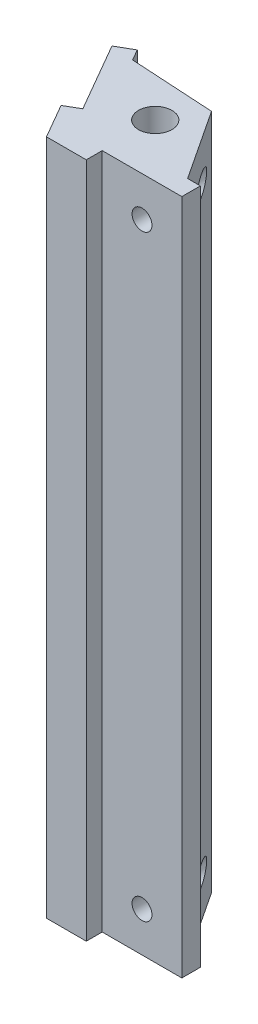
SolidWorks part; units mm, degrees
material "6061-T6 (SS)"
ref_plane "Front Plane" through (0, 0, 0) normal (0, 0, 1) x (1, 0, 0)
ref_plane "Top Plane" through (0, 0, 0) normal (0, 1, 0) x (1, 0, 0)
ref_plane "Right Plane" through (0, 0, 0) normal (1, 0, 0) x (0, 0, -1)
sketch "Sketch1" plane through (0, 0, 0) normal (0, 1, 0) x (1, 0, 0)
  line L0 (0, 0) -> (15, 0)
  line L1 (0, 0) -> (-7.5, 12.9904)
  line L2 (15, 0) -> (15, 4.3301)
  line L3 (0, 0) -> (2.5, 4.3301) construction
  line L4 (15, 4.3301) -> (13.3979, 4.3301)
  line L5 (-2.949, 13.768) -> (-3.75, 15.1554)
  line L6 (-3.75, 15.1554) -> (-7.5, 12.9904)
  line L7 (-2.949, 13.768) -> (7.5874, 13.1418)
  line L8 (7.5874, 13.1418) -> (13.3979, 4.3301)
  line L9 (2.5, 4.3301) -> (7.5874, 13.1418) construction
  line L10 (-2.949, 13.768) -> (2.5, 4.3301) construction
  line L11 (2.5, 4.3301) -> (13.3979, 4.3301) construction
  dimension "D1" = 5
  dimension "D2" = 15
  dimension "D3" = 240
extrude "Boss-Extrude1" add sketch "Sketch1" along normal blind 85
sketch "Sketch3" plane through (0, 85, 0) normal (0, 1, 0) x (1, 0, 0)
  line L0 (-7.5, 12.9904) -> (-5.7679, 13.9904)
  line L1 (-3.75, 15.1554) -> (-7.5, 12.9904) construction
  line L2 (-5.7679, 13.9904) -> (-0.7679, 5.3301)
  line L3 (-0.7679, 5.3301) -> (-2.5, 4.3301)
  line L4 (-7.5, 12.9904) -> (0, 0) construction
  line L5 (-2.5, 4.3301) -> (-7.5, 12.9904)
  line L6 (15, 0) -> (15, 2)
  line L7 (15, 0) -> (15, 4.3301) construction
  line L8 (15, 2) -> (5, 2)
  line L9 (5, 2) -> (5, 0)
  line L11 (5, 0) -> (15, 0)
  line L12 (0, 0) -> (15, 0) construction
  dimension "D1" = 2
  dimension "D2" = 5
extrude "Cut-Extrude1" cut sketch "Sketch3" against normal through all
sketch "Sketch4" plane through (0, 85, 0) normal (0, 1, 0) x (1, 0, 0)
  line L0 (0, 0) -> (7.5874, 13.1418) construction
  point P4 (5, 8.6603)
  dimension "D1" = 10
hole_wizard "M5x0.8 Tapped Hole1" positions "Sketch6" profile "Sketch7" tap size "M5x0.8" standard "ANSI Metric"
sketch "Sketch6" plane through (0, 85, 0) normal (0, 1, 0) x (1, 0, 0)
  point P0 (5, 8.6603)
sketch "Sketch7" plane through (5, 85, -8.6603) normal (1, 0, 0) x (0, 0, 1)
  line L0 (0, 0) -> (0, 17.2618)
  line L1 (0, 17.2618) -> (2.1, 16)
  line L2 (2.1, 16) -> (2.1, 0)
  line L5 (2.1, 0) -> (0, 0)
  line L10 (0, 17.2618) -> (-2.1, 16) construction
  line L11 (0, -6.35) -> (0, 107.95) construction
  dimension "Tap Drill Dia." = 4.2
  dimension "Tap Drill Depth" = 16
  dimension "Drill Angle" = 118
cosmetic thread "Hole Thread1" parameters "D1"=14, "D2"=5
ref_point "Point1"
hole_wizard "M5x0.8 Tapped Hole2" positions "Sketch11" profile "Sketch10" tap size "M5x0.8" standard "ANSI Metric"
sketch "Sketch11" plane through (0, 0, 0) normal (0, -1, 0) x (-1, 0, 0)
  point P0 (-5, 8.6603)
sketch "Sketch10" plane through (5, 0, -8.6603) normal (1, 0, 0) x (0, 0, -1)
  line L0 (0, 0) -> (0, 17.6618)
  line L1 (0, 17.6618) -> (2.1, 16.4)
  line L2 (2.1, 16.4) -> (2.1, 0)
  line L5 (2.1, 0) -> (0, 0)
  line L10 (0, 17.6618) -> (-2.1, 16.4) construction
  line L11 (0, -6.35) -> (0, 107.95) construction
  dimension "Tap Drill Dia." = 4.2
  dimension "Tap Drill Depth" = 16.4
  dimension "Drill Angle" = 118
cosmetic thread "Hole Thread2" parameters "D1"=14, "D2"=5
sketch "Sketch12" plane through (1.7321, 0, -1) normal (-0.866, 0, 0.5) x (0.5, 0, 0.866)
  line L0 (-15, 42.5) -> (-5, 42.5) construction
  line L1 (-15, 0) -> (-15, 85) construction
  line L2 (-5, 0) -> (-5, 85) construction
  line L3 (-10, 80) -> (-10, 5) construction
  point P8 (-10, 42.5)
  dimension "D1" = 75
hole_wizard "M3x0.5 Tapped Hole1" positions "Sketch14" profile "Sketch13" tap size "M3x0.5" standard "ANSI Metric" end condition through all
sketch "Sketch14" plane through (1.7321, 0, -1) normal (-0.866, 0, 0.5) x (0.5, 0, 0.866)
  point P0 (-10, 80)
  point P3 (-10, 5)
sketch "Sketch13" plane through (-3.2679, 80, -9.6603) normal (0, 1, 0) x (0.5, 0, 0.866)
  line L0 (0, 0) -> (0, 18.5681)
  line L1 (0, 18.5681) -> (1.25, 18.5681)
  line L2 (1.25, 18.5681) -> (1.25, 0)
  line L5 (1.25, 0) -> (0, 0)
  line L11 (0, -6.35) -> (0, 107.95) construction
  dimension "Thru Tap Drill Dia." = 2.5
  dimension "Thru Tap Drill Depth" = 18.5681
cosmetic thread "Hole Thread3" parameters "D2"=3
cosmetic thread "Hole Thread4" parameters "D2"=3
sketch "Sketch15" plane through (0, 0, -2) normal (0, 0, 1) x (1, 0, 0)
  line L0 (5, 42.5) -> (15, 42.5) construction
  line L1 (5, 0) -> (5, 85) construction
  line L2 (15, 0) -> (15, 85) construction
  line L3 (10, 80) -> (10, 5) construction
  point P8 (10, 42.5)
  dimension "D1" = 75
hole_wizard "M3x0.5 Tapped Hole2" positions "Sketch17" profile "Sketch16" tap size "M3x0.5" standard "ANSI Metric" end condition through all
sketch "Sketch17" plane through (0, 0, -2) normal (0, 0, 1) x (1, 0, 0)
  point P0 (10, 80)
  point P3 (10, 5)
sketch "Sketch16" plane through (10, 80, -2) normal (1, 0, 0) x (0, -1, 0)
  line L0 (0, 0) -> (0, 13.1554)
  line L1 (0, 13.1554) -> (1.25, 13.1554)
  line L2 (1.25, 13.1554) -> (1.25, 0)
  line L5 (1.25, 0) -> (0, 0)
  line L11 (0, -6.35) -> (0, 107.95) construction
  dimension "Thru Tap Drill Dia." = 2.5
  dimension "Thru Tap Drill Depth" = 13.1554
cosmetic thread "Hole Thread5" parameters "D2"=3
cosmetic thread "Hole Thread6" parameters "D2"=3
